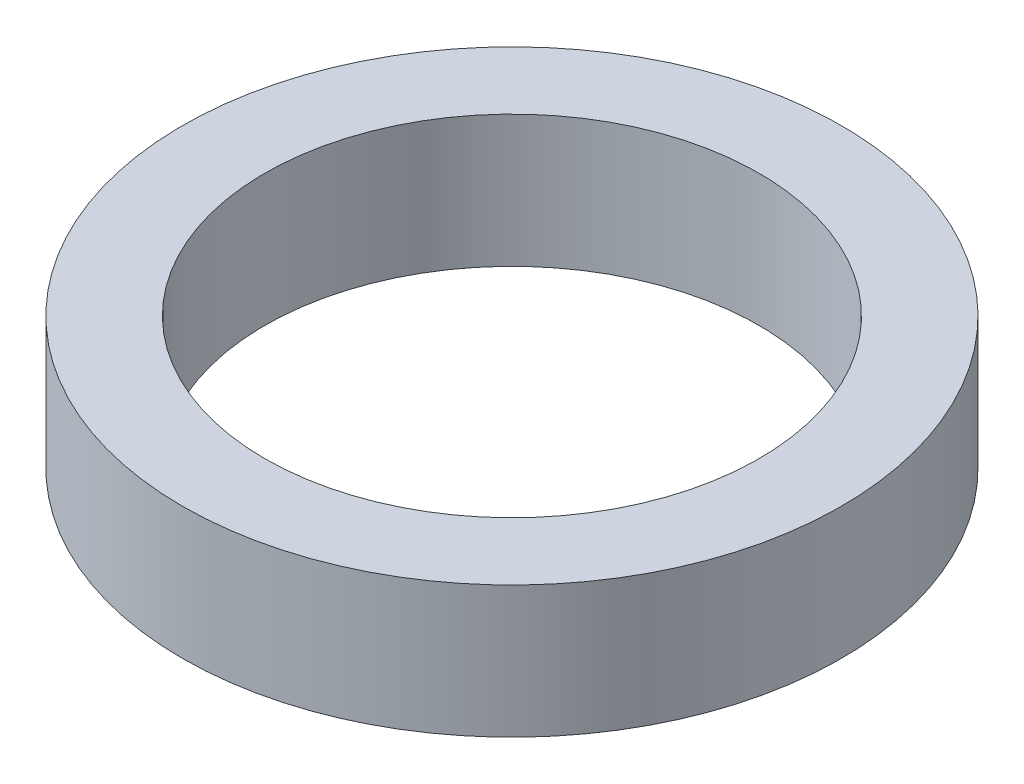
SolidWorks part; units mm, degrees
ref_plane "Front Plane" through (0, 0, 0) normal (0, 0, 1) x (1, 0, 0)
ref_plane "Top Plane" through (0, 0, 0) normal (0, 1, 0) x (1, 0, 0)
ref_plane "Right Plane" through (0, 0, 0) normal (1, 0, 0) x (0, 0, -1)
sketch "Sketch1" plane through (0, 0, 0) normal (0, 1, 0) x (1, 0, 0)
  circle A0 centre (0, 0) radius 60
  dimension "FLANGE_OD" = 120
extrude "Boss-Extrude1" add sketch "Sketch1" along normal blind 24
sketch "Sketch2" plane through (0, 0, 0) normal (0, 1, 0) x (1, 0, 0)
  circle A0 centre (0, 0) radius 45
  dimension "BORE_D" = 90
extrude "Cut-Extrude1" cut sketch "Sketch2" along normal through all
sketch "Sketch3" plane through (0, 24, 0) normal (0, 1, 0) x (1, 0, 0)
  circle A0 centre (0, 0) radius 26.3702 construction
  circle A1 centre (-26.3702, 0) radius 1.8455
  dimension "BOLT_D" = 3.691
  dimension "BOLT_PCD" = 52.7404
extrude "Cut-Extrude2" cut sketch "Sketch3" against normal blind 22.0787 rebuild error yes
pattern_circular "CirPattern1" count 5 over 360 rebuild error yes
